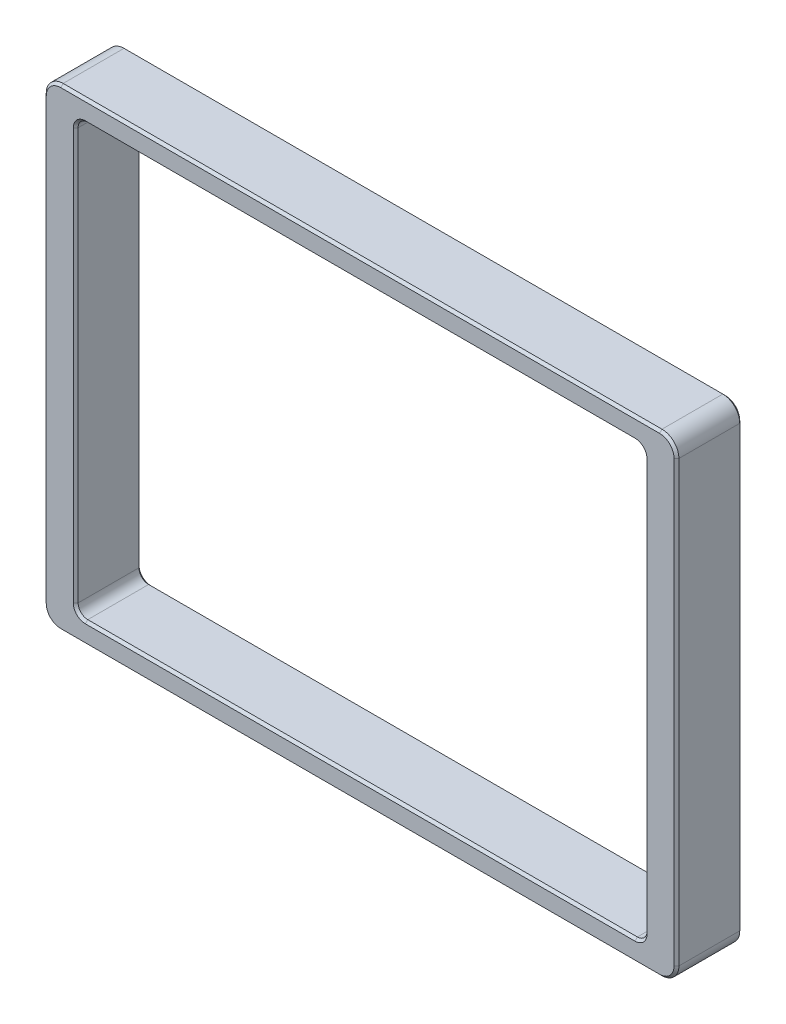
SolidWorks part; units mm, degrees
ref_plane "Front" through (0, 0, 0) normal (0, 0, 1) x (1, 0, 0)
ref_plane "Top" through (0, 0, 0) normal (0, 1, 0) x (1, 0, 0)
ref_plane "Right" through (0, 0, 0) normal (1, 0, 0) x (0, 0, -1)
sketch "Sketch1" plane through (0, 0, 0) normal (0, 0, 1) x (1, 0, 0)
  line L12 (-65.5, 45.5) -> (-65.5, -45.5)
  line L13 (-62, -49) -> (62, -49)
  line L14 (65.5, -45.5) -> (65.5, 45.5)
  line L15 (62, 49) -> (-62, 49)
  line L16 (-65.5, 45.5) -> (-65.5, -45.5)
  line L17 (-62, -49) -> (62, -49)
  line L18 (65.5, -45.5) -> (65.5, 45.5)
  line L19 (62, 49) -> (-62, 49)
  line L25 (-56.9, 44.6) -> (56.9, 44.6)
  line L26 (-58.9, 42.6) -> (-58.9, -42.6)
  line L27 (-56.9, -44.6) -> (56.9, -44.6)
  line L28 (58.9, 42.6) -> (58.9, -42.6)
  line L29 (-58.9, 44.6) -> (58.9, -44.6) construction
  line L30 (-58.9, -44.6) -> (58.9, 44.6) construction
  arc A8 (-62, 49) -> (-65.5, 45.5) centre (-62, 45.5) ccw
  arc A9 (-65.5, -45.5) -> (-62, -49) centre (-62, -45.5) ccw
  arc A10 (62, -49) -> (65.5, -45.5) centre (62, -45.5) ccw
  arc A11 (65.5, 45.5) -> (62, 49) centre (62, 45.5) ccw
  arc A12 (-62, 49) -> (-65.5, 45.5) centre (-62, 45.5) ccw
  arc A13 (-65.5, -45.5) -> (-62, -49) centre (-62, -45.5) ccw
  arc A14 (62, -49) -> (65.5, -45.5) centre (62, -45.5) ccw
  arc A15 (65.5, 45.5) -> (62, 49) centre (62, 45.5) ccw
  arc A21 (56.9, -44.6) -> (58.9, -42.6) centre (56.9, -42.6) ccw
  arc A22 (56.9, 44.6) -> (58.9, 42.6) centre (56.9, 42.6) cw
  arc A23 (-56.9, 44.6) -> (-58.9, 42.6) centre (-56.9, 42.6) ccw
  arc A24 (-58.9, -42.6) -> (-56.9, -44.6) centre (-56.9, -42.6) ccw
  point P0 (0, 0)
  dimension "D4" = 2
  dimension "D2" = 6.6
  dimension "D3" = 4.4
  dimension "D1" = 0.5
extrude "Boss-Extrude1" add sketch "Sketch1" along normal up to surface (13.6 mm away)
chamfer "Deburs" distance 0.5 angle 45 32 edges at (-64.4749, 47.9749, 13.6) (0, 49, 13.6) (64.4749, 47.9749, 13.6) (65.5, 0, 13.6) (64.4749, -47.9749, 13.6) (0, -49, 13.6) (-64.4749, -47.9749, 13.6) (-65.5, 0, 13.6) (58.9, 0, 13.6) (58.3142, 44.0142, 13.6) (0, 44.6, 13.6) (-58.3142, 44.0142, 13.6) (-58.9, 0, 13.6) (-58.3142, -44.0142, 13.6) (0, -44.6, 13.6) (58.3142, -44.0142, 13.6) (0, -44.6, 0) (-58.3142, -44.0142, 0) (-58.9, 0, 0) (-58.3142, 44.0142, 0) (0, 44.6, 0) (58.3142, 44.0142, 0) (58.9, 0, 0) (58.3142, -44.0142, 0) (-65.5, 0, 0) (-64.4749, -47.9749, 0) (0, -49, 0) (64.4749, -47.9749, 0) (65.5, 0, 0) (64.4749, 47.9749, 0) (0, 49, 0) (-64.4749, 47.9749, 0)
